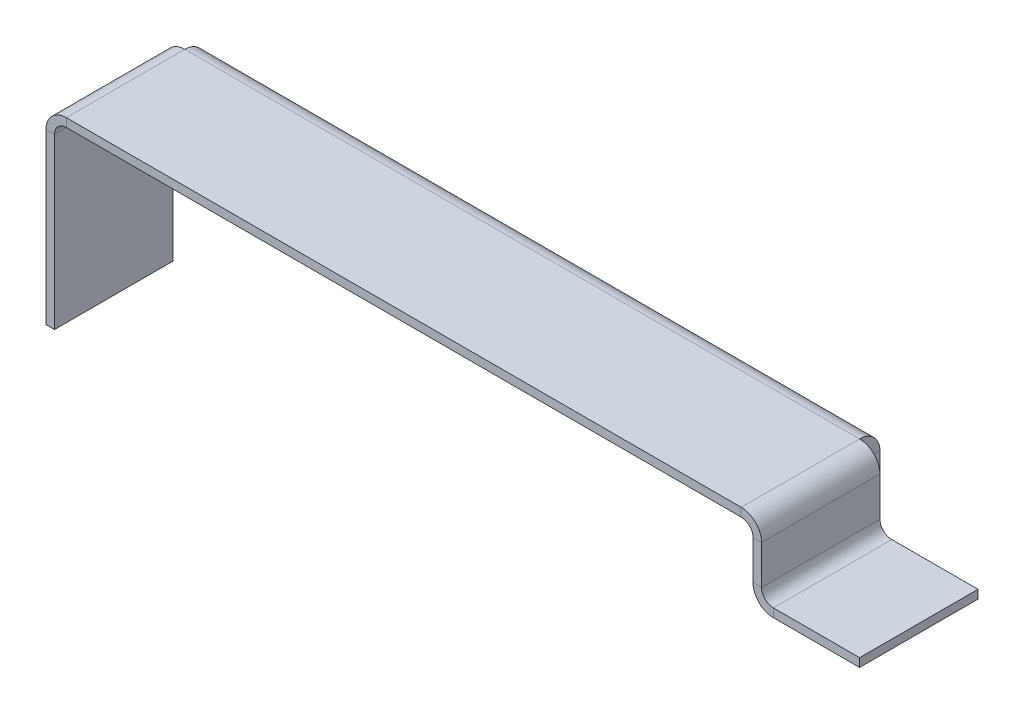
SolidWorks part; units mm, degrees
note: The reader was unsure of these and kept them because the rebuilt part matched: flange length of "Edge-Flange1", "Edge-Flange2", "Edge-Flange3", "Edge-Flange4".
material "1060 Alloy"
ref_plane "Front" through (0, 0, 0) normal (0, 0, 1) x (1, 0, 0)
ref_plane "Top" through (0, 0, 0) normal (0, 1, 0) x (1, 0, 0)
ref_plane "Right" through (0, 0, 0) normal (1, 0, 0) x (0, 0, -1)
sketch "Sketch1" plane through (0, 0, 0) normal (0, 1, 0) x (1, 0, 0)
  line L1 (0, 0) -> (72.39, 0)
  line L2 (0, 0) -> (0, 12.7)
  line L3 (0, 12.7) -> (72.39, 12.7)
  line L4 (72.39, 0) -> (72.39, 12.7)
  dimension "D1" = 12.7
  dimension "D2" = 72.39
base flange "Base-Flange1" sketch "Sketch1" thickness 0.9119 reverse thickness direction no parameters "D1"=1.27
edge flange "Edge-Flange1" sketch "Sketch8" flange angle 90 flange length 20.32 flange position bend outside bend radius 1.27 thickness 0.9119 relief rectangular parameters "D6"=10
sketch "Sketch8" plane through (0, -0.9119, 0) normal (1, 0, 0) x (0, 0, 1)
  line L1 (0, 0) -> (-12.7, 0) construction
  line L2 (-12.7, 0) -> (-12.7, 19.4081)
  line L3 (-12.7, 19.4081) -> (0, 19.4081)
  line L4 (0, 19.4081) -> (0, 0)
  line L5 (0, 0) -> (-12.7, 0)
bend "EdgeBend1" bend radius 1.27 bend angle 90 parameters "D5"=1
edge flange "Edge-Flange2" sketch "Sketch11" flange angle 90 flange length 6.35 flange position bend outside bend radius 1.27 thickness 0.9119 relief rectangular parameters "D6"=10
sketch "Sketch11" plane through (72.39, -0.9119, 0) normal (1, 0, 0) x (0, 0, 1)
  line L0 (0, 0) -> (-12.7, 0) construction
  line L1 (0, 0) -> (-12.7, 0)
  line L2 (-12.7, 0) -> (-12.7, 5.4381)
  line L3 (-12.7, 5.4381) -> (0, 5.4381)
  line L4 (0, 5.4381) -> (0, 0)
bend "EdgeBend2" bend radius 1.27 bend angle 90 parameters "D5"=2
edge flange "Edge-Flange3" sketch "Sketch14" flange angle 90 flange length 11.43 flange position bend outside bend radius 1.27 thickness 0.9119 relief rectangular parameters "D6"=10
sketch "Sketch14" plane through (74.5719, -6.35, 0) normal (0, -1, 0) x (0, 0, -1)
  line L0 (0, 0) -> (12.7, 0) construction
  line L1 (0, 0) -> (12.7, 0)
  line L2 (0, 0) -> (0, 10.5181)
  line L3 (0, 10.5181) -> (12.7, 10.5181)
  line L4 (12.7, 10.5181) -> (12.7, 0)
bend "EdgeBend3" bend radius 1.27 bend angle 90 parameters "D5"=3
edge flange "Edge-Flange4" sketch "Sketch17" flange angle 90 flange length 6.35 flange position bend outside bend radius 1.27 thickness 0.9119 relief rectangular parameters "D6"=10
sketch "Sketch17" plane through (0, -0.9119, -12.7) normal (0, 0, -1) x (1, 0, 0)
  line L2 (0, 0) -> (0, 5.4381)
  line L3 (0, 5.4381) -> (72.39, 5.4381)
  line L4 (72.39, 5.4381) -> (72.39, 0)
  line L7 (72.39, 0) -> (0, 0) construction
  line L8 (72.39, 0) -> (0, 0)
bend "EdgeBend4" bend radius 1.27 bend angle 90 parameters "D5"=4
sketch "Bend-Lines1" [suppressed] plane through (0, 0, 0) normal (0, 1, 0) x (1, 0, 0)
sketch "Bounding-Box1" [suppressed] plane through (0, 0, 0) normal (0, 1, 0) x (1, 0, 0)
sheet metal parameters "Sheet-Metal1" thickness 0.9119 parameters "D1"=1.27
flat pattern "Flat-Pattern1" [suppressed]
sketch "Bend-Lines2" plane through (0, 0, 0) normal (0, 1, 0) x (1, 0, 0)
sketch3d "Bounding-Box2" [suppressed]
  line L0 (-73.66, 12.7, 0) -> (0, 12.7, 0) construction
  line L1 (-73.66, 0, 0) -> (0, 0, 0) construction
  line L2 (-73.66, 12.7, 0) -> (-73.66, 0, 0) construction
  line L3 (0, 12.7, 0) -> (0, 0, 0) construction
sheet metal parameters "Sheet-Metal2" thickness 0.9119 parameters "D1"=1.27
flat pattern "Flat-Pattern1"
sketch "Bend-Lines2" plane through (0, 0, 0) normal (0, 1, 0) x (1, 0, 0)
  line L0 (-1.3555, 12.7) -> (-1.3555, 0) construction
  line L1 (-1.3555, 12.7) -> (-1.3555, 0) construction
sketch3d "Bounding-Box2" [suppressed]
  line L0 (73.66, 12.7, 0) -> (-20.8492, 12.7, 0) construction
  line L1 (73.66, 0, 0) -> (-20.8492, 0, 0) construction
  line L2 (73.66, 12.7, 0) -> (73.66, 0, 0) construction
  line L3 (-20.8492, 12.7, 0) -> (-20.8492, 0, 0) construction
bend of the flat pattern "Flatten-<EdgeBend1>1"
sheet metal parameters "Sheet-Metal3" thickness 0.9119 parameters "D1"=1.27
flat pattern "Flat-Pattern1"
sketch "Bend-Lines2" plane through (0, 0, 0) normal (0, 1, 0) x (1, 0, 0)
  line L0 (-1.3555, 12.7) -> (-1.3555, 0) construction
  line L1 (-1.3555, 12.7) -> (-1.3555, 0) construction
  line L2 (75.0155, 0) -> (75.0155, 12.7) construction
  line L3 (75.0155, 0) -> (75.0155, 12.7) construction
sketch3d "Bounding-Box2" [suppressed]
  line L0 (81.8092, 12.7, 0) -> (-20.8492, 12.7, 0) construction
  line L1 (81.8092, 0, 0) -> (-20.8492, 0, 0) construction
  line L2 (81.8092, 12.7, 0) -> (81.8092, 0, 0) construction
  line L3 (-20.8492, 12.7, 0) -> (-20.8492, 0, 0) construction
bend of the flat pattern "Flatten-<EdgeBend1>1"
bend of the flat pattern "Flatten-<EdgeBend2>1"
sheet metal parameters "Sheet-Metal4" thickness 0.9119 parameters "D1"=1.27
flat pattern "Flat-Pattern1"
sketch "Bend-Lines2" plane through (0, 0, 0) normal (0, 1, 0) x (1, 0, 0)
  line L0 (-1.3555, 12.7) -> (-1.3555, 0) construction
  line L1 (-1.3555, 12.7) -> (-1.3555, 0) construction
  line L2 (75.0155, 0) -> (75.0155, 12.7) construction
  line L3 (75.0155, 0) -> (75.0155, 12.7) construction
  line L4 (83.1648, 0) -> (83.1648, 12.7) construction
  line L5 (83.1648, 0) -> (83.1648, 12.7) construction
sketch3d "Bounding-Box2" [suppressed]
  line L0 (95.0384, 12.7, 0) -> (-20.8492, 12.7, 0) construction
  line L1 (95.0384, 0, 0) -> (-20.8492, 0, 0) construction
  line L2 (95.0384, 12.7, 0) -> (95.0384, 0, 0) construction
  line L3 (-20.8492, 12.7, 0) -> (-20.8492, 0, 0) construction
bend of the flat pattern "Flatten-<EdgeBend1>1"
bend of the flat pattern "Flatten-<EdgeBend2>1"
bend of the flat pattern "Flatten-<EdgeBend3>1"
sheet metal parameters "Sheet-Metal5" thickness 0.9119 parameters "D1"=1.27
flat pattern "Flat-Pattern1"
sketch "Bend-Lines2" plane through (0, 0, 0) normal (0, 1, 0) x (1, 0, 0)
  line L0 (-1.3555, 12.7) -> (-1.3555, 0) construction
  line L1 (-1.3555, 12.7) -> (-1.3555, 0) construction
  line L2 (73.7455, 0) -> (73.7455, 12.7) construction
  line L3 (73.7455, 0) -> (73.7455, 12.7) construction
  line L4 (80.6248, 0) -> (80.6248, 12.7) construction
  line L5 (80.6248, 0) -> (80.6248, 12.7) construction
  line L6 (72.39, 14.0555) -> (0, 14.0555) construction
  line L7 (72.39, 14.0555) -> (0, 14.0555) construction
sketch3d "Bounding-Box2" [suppressed]
  line L0 (91.2284, 19.5792, 0) -> (-20.8492, 19.5792, 0) construction
  line L1 (91.2284, 0, 0) -> (-20.8492, 0, 0) construction
  line L2 (91.2284, 19.5792, 0) -> (91.2284, 0, 0) construction
  line L3 (-20.8492, 19.5792, 0) -> (-20.8492, 0, 0) construction
bend of the flat pattern "Flatten-<EdgeBend1>1"
bend of the flat pattern "Flatten-<EdgeBend2>1"
bend of the flat pattern "Flatten-<EdgeBend3>1"
bend of the flat pattern "Flatten-<EdgeBend4>1"
